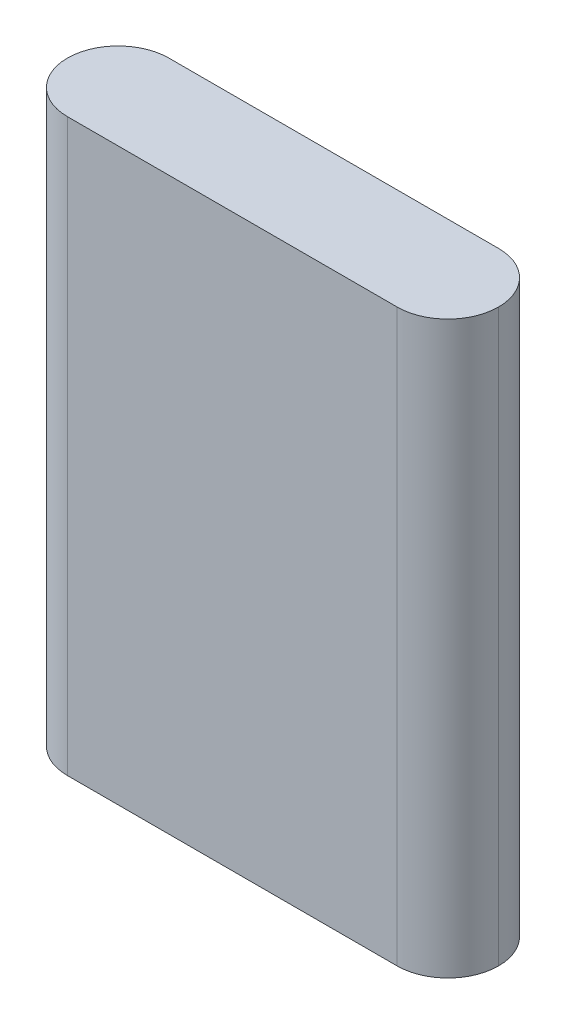
SolidWorks part; units mm, degrees
material "1060-H12"
ref_plane "Front Plane" through (0, 0, 0) normal (0, 0, 1) x (1, 0, 0)
ref_plane "Top Plane" through (0, 0, 0) normal (0, 1, 0) x (1, 0, 0)
ref_plane "Right Plane" through (0, 0, 0) normal (1, 0, 0) x (0, 0, -1)
sketch "Sketch1" plane through (0, 0, 0) normal (0, 0, 1) x (1, 0, 0)
  line L1 (0, 0) -> (34, 0)
  line L2 (0, 0) -> (0, 45)
  line L3 (0, 45) -> (34, 45)
  line L4 (34, 0) -> (34, 45)
  dimension "D1" = 34
  dimension "D2" = 45
extrude "Boss-Extrude1" add sketch "Sketch1" along normal blind 8
fillet "Fillet1" radius 4 4 edges at (34, 22.5, 8) (34, 22.5, 0) (0, 22.5, 0) (0, 22.5, 8)
